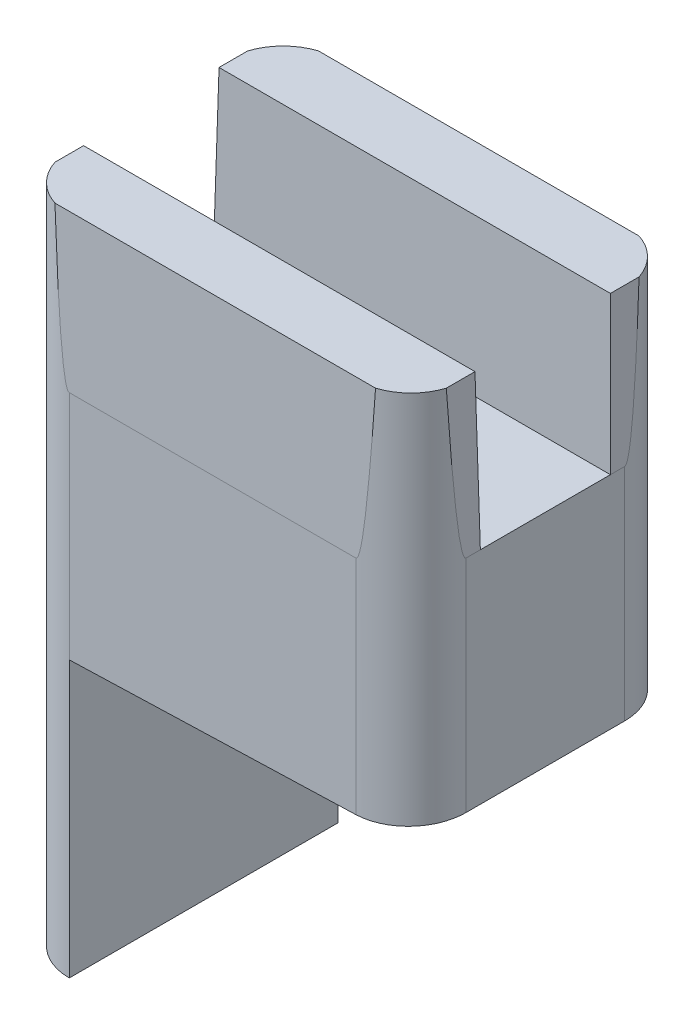
SolidWorks part; units mm, degrees
ref_plane "Front Plane" through (0, 0, 0) normal (0, 0, 1) x (1, 0, 0)
ref_plane "Top Plane" through (0, 0, 0) normal (0, 1, 0) x (1, 0, 0)
ref_plane "Right Plane" through (0, 0, 0) normal (1, 0, 0) x (0, 0, -1)
sketch "Sketch1" plane through (0, 0, 0) normal (0, 0, 1) x (1, 0, 0)
  line L1 (0, 0) -> (5, 0)
  line L2 (0, 0) -> (0, 46)
  line L3 (0, 46) -> (36, 46)
  line L4 (36, 26) -> (36, 46)
  line L6 (5, 0) -> (5, 25)
  line L7 (5, 25) -> (36, 26)
  dimension "D1" = 46
  dimension "D2" = 36
  dimension "D3" = 5
  dimension "D4" = 25
  dimension "D5" = 1
extrude "Boss-Extrude1" add sketch "Sketch1" along normal blind 24.4
sketch "Sketch2" plane through (0, 46, 0) normal (0, 1, 0) x (1, 0, 0)
  line L0 (36, -24.4) -> (36, 0) construction
  line L1 (0, 0) -> (36, 0)
  line L2 (0, 0) -> (0, -6.3)
  line L3 (0, -6.3) -> (36, -6.3)
  line L4 (36, 0) -> (36, -6.3)
  line L6 (0, -24.4) -> (36, -24.4)
  line L7 (0, -24.4) -> (0, -18.1)
  line L8 (0, -18.1) -> (36, -18.1)
  line L9 (36, -24.4) -> (36, -18.1)
  dimension "D1" = 11.8
extrude "Boss-Extrude2" add sketch "Sketch2" along normal blind 14 draft 1
fillet "Fillet1" radius 5 4 edges at (36, 36, 24.4) (36, 36, 0) (0, 23, 0) (0, 23, 24.4)
